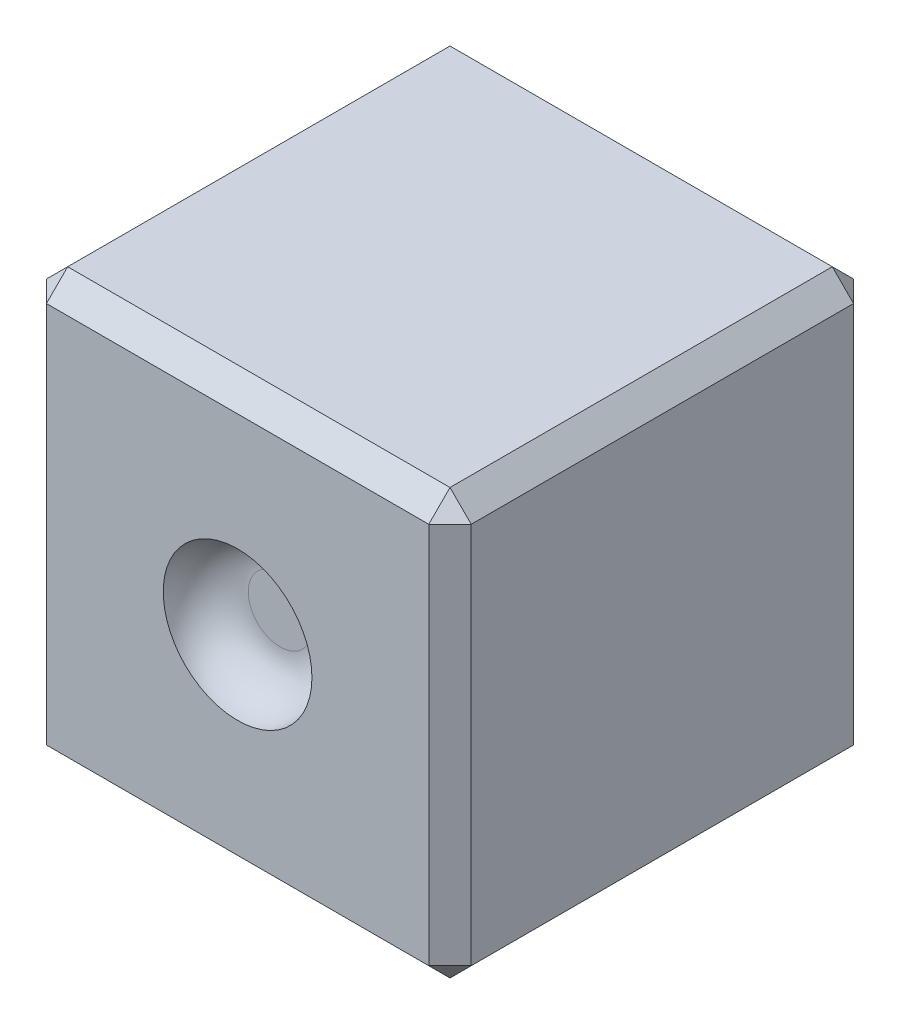
SolidWorks part; units mm, degrees
ref_plane "正面" through (0, 0, 0) normal (0, 0, 1) x (1, 0, 0)
ref_plane "平面" through (0, 0, 0) normal (0, 1, 0) x (1, 0, 0)
ref_plane "右側面" through (0, 0, 0) normal (1, 0, 0) x (0, 0, -1)
sketch "ｽｹｯﾁ2" plane through (0, 0, 0) normal (0, 0, 1) x (1, 0, 0)
  line L1 (-24.5865, 15.1692) -> (-4.5865, 15.1692)
  line L2 (-24.5865, 15.1692) -> (-24.5865, -4.8308)
  line L3 (-24.5865, -4.8308) -> (-4.5865, -4.8308)
  line L4 (-4.5865, 15.1692) -> (-4.5865, -4.8308)
  dimension "D1" = 20
  dimension "D2" = 20
extrude "ﾎﾞｽ - 押し出し1" add sketch "ｽｹｯﾁ2" along normal blind 20
chamfer "面取り2" distance 1 angle 45 9 edges at (-4.5865, 5.1692, 0) (-14.5865, 15.1692, 0) (-24.5865, 5.1692, 20) (-14.5865, -4.8308, 20) (-24.5865, 15.1692, 10) (-14.5865, 15.1692, 20) (-4.5865, 15.1692, 10) (-4.5865, 5.1692, 20) (-4.5865, -4.8308, 10)
sketch "ｽｹｯﾁ3" plane through (0, 0, 20) normal (0, 0, 1) x (1, 0, 0)
  line L0 (-23.5865, 15.1692) -> (-5.5865, 15.1692) construction
  line L1 (-24.5865, -4.8308) -> (-24.5865, 14.1692) construction
  circle A0 centre (-14.5865, 5.1692) radius 3.5
  dimension "D1" = 7
  dimension "D2" = 10
  dimension "D3" = 10
extrude "ｶｯﾄ - 押し出し1" cut sketch "ｽｹｯﾁ3" against normal blind 2
fillet "ﾌｨﾚｯﾄ1" radius 2 1 edges at (-11.0865, 5.1692, 18)
